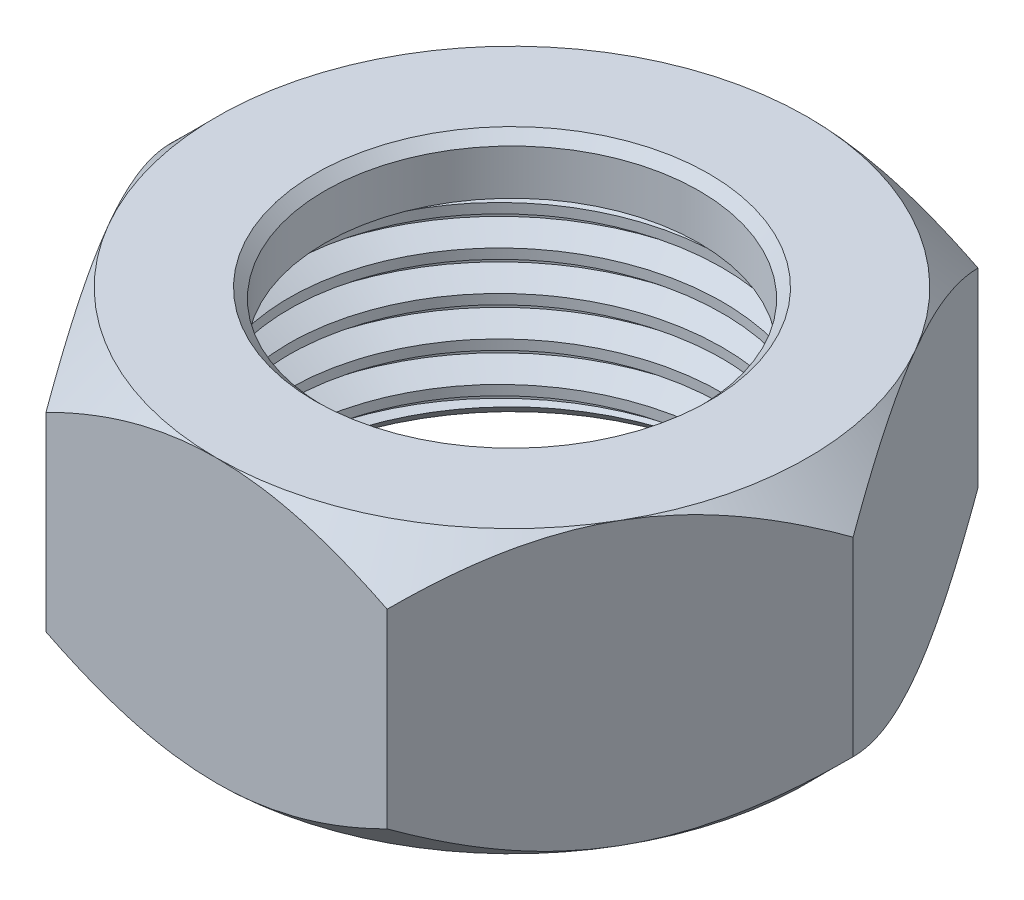
SolidWorks part; units mm, degrees
material "AISI 4130 Steel, annealed at 865C"
ref_plane "Front Plane" through (0, 0, 0) normal (0, 0, 1) x (1, 0, 0)
ref_plane "Top Plane" through (0, 0, 0) normal (0, 1, 0) x (1, 0, 0)
ref_plane "Right Plane" through (0, 0, 0) normal (1, 0, 0) x (0, 0, -1)
sketch "Sketch1" plane through (0, 0, 0) normal (0, 1, 0) x (1, 0, 0)
  line L1 (17.3205, 0) -> (8.6603, 15)
  line L2 (8.6603, 15) -> (-8.6603, 15)
  line L3 (-8.6603, 15) -> (-17.3205, 0)
  line L4 (-17.3205, 0) -> (-8.6603, -15)
  line L5 (-8.6603, -15) -> (8.6603, -15)
  line L6 (8.6603, -15) -> (17.3205, 0)
  circle A0 centre (0, 0) radius 15 construction
  dimension "D1" = 30
extrude "Boss-Extrude1" add sketch "Sketch1" along normal blind 14.3
sketch "Sketch2" plane through (0, 14.3, 0) normal (0, 1, 0) x (1, 0, 0)
  circle A0 centre (0, 0) radius 9.5
  dimension "D1" = 19
extrude "Cut-Extrude1" cut sketch "Sketch2" against normal blind 14.3
sketch "Sketch6" plane through (0, 0, 0) normal (0, -1, 0) x (1, 0, 0)
  circle A0 centre (0, 0) radius 11
  dimension "D1" = 22
extrude "Cut-Extrude2" cut sketch "Sketch6" against normal blind 11.5
sketch "Sketch7" plane through (0, 14.3, 0) normal (0, 1, 0) x (1, 0, 0)
  circle A0 centre (0, 0) radius 15
extrude "Cut-Extrude3" cut sketch "Sketch7" against normal blind 11.5 draft 45 flip side to cut
sketch "Sketch8" plane through (0, 0, 0) normal (0, -1, 0) x (1, 0, 0)
  circle A0 centre (0, 0) radius 15
extrude "Cut-Extrude4" cut sketch "Sketch8" against normal blind 11.5 draft 45 flip side to cut
chamfer "Chamfer1" distance 1.5 angle 45 1 edges at (0, 0, -11)
chamfer "Chamfer2" distance 0.5 angle 45 1 edges at (0, 14.3, 9.5)
thread "Thread1" pitch 2 method cut profile "Thread Profile1" start angle 0, offset 4, length 0, pitch 2, diameter 22
ref_plane "Plane1" through (11, -2.5, 0) normal (0, 0, 1) x (1, 0, 0)
sketch "Thread Profile1" plane through (11, -2.5, 0) normal (0, 0, 1) x (1, 0, 0)
  line L0 (0, 0) -> (0, 2) construction
  line L1 (0, 0) -> (1.0825, 0.625)
  line L2 (1.0825, 0.625) -> (1.0825, 0.875)
  line L3 (1.0825, 0.875) -> (0, 1.5)
  line L4 (1.0825, 0.75) -> (0, 0.75) construction
  line L11 (0, 0) -> (0, 1.5)
  point P2 (0, 0)
  dimension "Pitch" = 2
  dimension "Profile_Angle" = 60
  dimension "Profile_Land" = 0.25
  dimension "Profile_Height" = 1.0825
